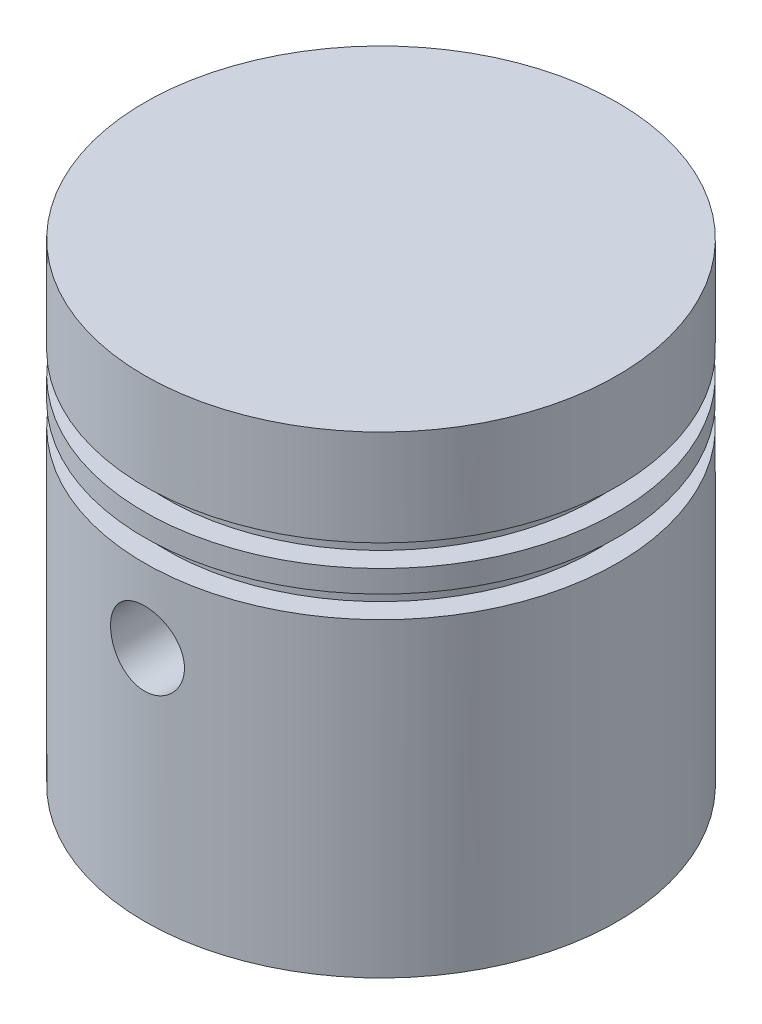
SolidWorks part; units mm, degrees
material "6061 Alloy"
ref_plane "Front Plane" through (0, 0, 0) normal (0, 0, 1) x (1, 0, 0)
ref_plane "Top Plane" through (0, 0, 0) normal (0, 1, 0) x (1, 0, 0)
ref_plane "Right Plane" through (0, 0, 0) normal (1, 0, 0) x (0, 0, -1)
sketch "Sketch1" plane through (0, 0, 0) normal (0, 1, 0) x (1, 0, 0)
  circle A0 centre (0, 0) radius 8
  dimension "D1" = 16
extrude "Boss-Extrude1" add sketch "Sketch1" along normal blind 16
sketch "Sketch2" plane through (0, 0, 0) normal (0, -1, 0) x (1, 0, 0)
  circle A0 centre (0, 0) radius 6.5
  dimension "D1" = 13
extrude "Cut-Extrude1" cut sketch "Sketch2" against normal blind 5
sketch "Sketch3" plane through (0, 0, 0) normal (0, -1, 0) x (1, 0, 0)
  circle A0 centre (0, 0) radius 5
  dimension "D1" = 10
extrude "Cut-Extrude2" cut sketch "Sketch3" against normal blind 12
sketch "Sketch4" plane through (0, 0, 0) normal (0, 0, 1) x (1, 0, 0)
  line L0 (8, 16) -> (-8, 16) construction
  circle A0 centre (0, 8) radius 1.25
  dimension "D1" = 2.5
  dimension "D2" = 8
  dimension "D3" = 8
extrude "Cut-Extrude3" cut sketch "Sketch4" against normal through all both and the other way through all
sketch "Sketch5" plane through (0, 0, 0) normal (0, -1, 0) x (1, 0, 0)
  circle A0 centre (0, 0) radius 8
  circle A1 centre (0, 0) radius 7.25
  dimension "D1" = 16
  dimension "D2" = 14.5
extrude "Cut-Extrude5" cut sketch "Sketch5" against normal blind 0.75 from offset 10.5 offset against normal yes
extrude "Cut-Extrude6" cut sketch "Sketch5<3>" against normal blind 0.75 from offset 12 offset against normal yes
sketch "Sketch5<3>" plane through (0, 0, 0) normal (0, -1, 0) x (1, 0, 0) same geometry as "Sketch5"
